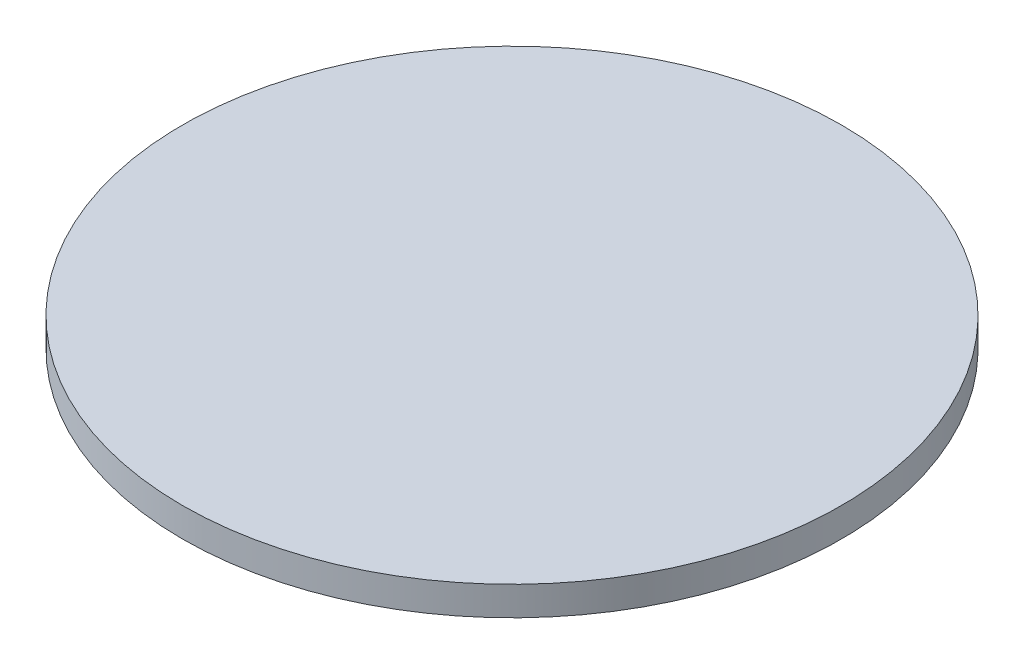
SolidWorks part; units mm, degrees
ref_plane "Front Plane" through (0, 0, 0) normal (0, 0, 1) x (1, 0, 0)
ref_plane "Top Plane" through (0, 0, 0) normal (0, 1, 0) x (1, 0, 0)
ref_plane "Right Plane" through (0, 0, 0) normal (1, 0, 0) x (0, 0, -1)
sketch "Sketch1" plane through (0, 0, 0) normal (0, 1, 0) x (1, 0, 0)
  circle A0 centre (0, 0) radius 11.35
  point P1 (0, 0)
  point P3 (0, 0)
  point P5 (0, 0)
  point P7 (-3.6105, -10.7604)
  point P8 (-3.4118, -10.7604)
  dimension "D1" = 22.7
extrude "Boss-Extrude1" add sketch "Sketch1" along normal blind 1
